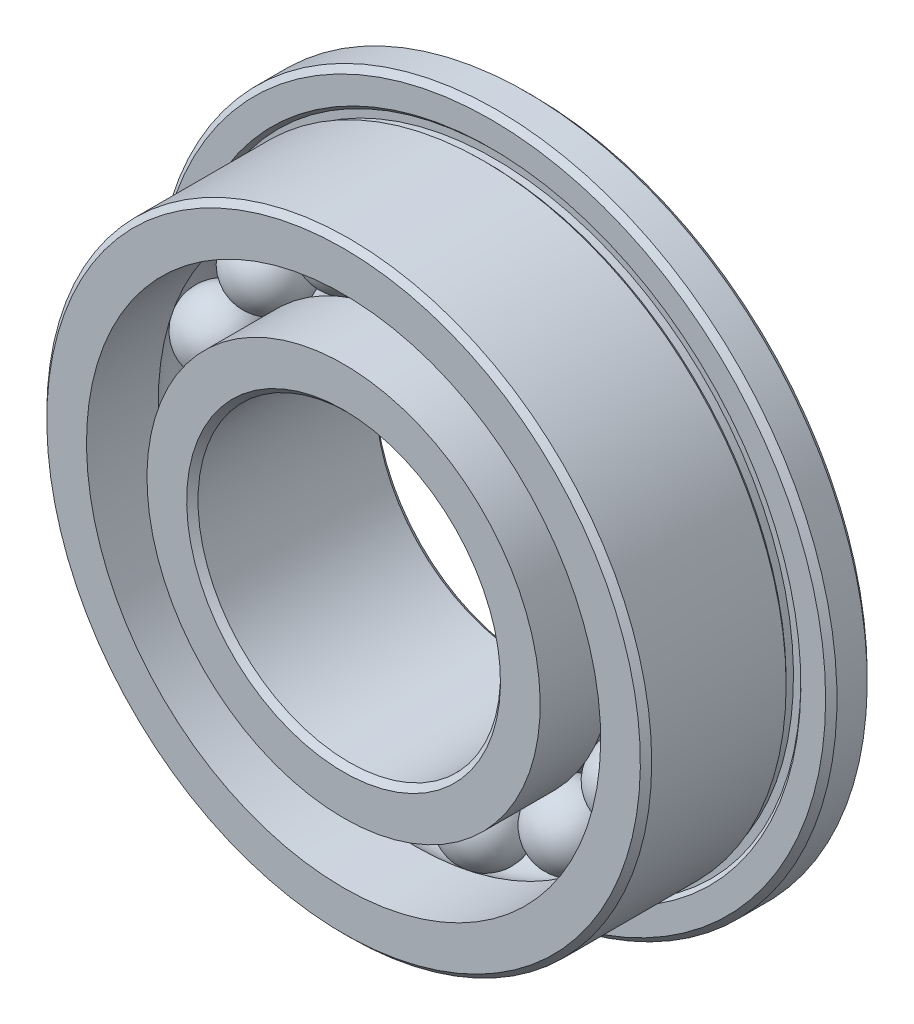
SolidWorks part; units mm, degrees
ref_plane "Front Plane" through (0, 0, 0) normal (0, 0, 1) x (1, 0, 0)
ref_plane "Top Plane" through (0, 0, 0) normal (0, 1, 0) x (1, 0, 0)
ref_plane "Right Plane" through (0, 0, 0) normal (1, 0, 0) x (0, 0, -1)
sketch "Sketch1" plane through (0, 0, 0) normal (1, 0, 0) x (0, 0, -1)
  line L0 (0, 8) -> (0, -8) construction
  line L1 (-2.5, 8) -> (2.5, 8) construction
  line L2 (0, 0) -> (2.5, 0) construction
  line L3 (2.5, 9) -> (2.5, -9) construction
  line L4 (2.5, -9) -> (1.4, -9) construction
  line L5 (2.5, 4) -> (0, 4) construction
  line L6 (2.5, 4) -> (2.5, -4) construction
  dimension "OD" = 16
  dimension "Width" = 5
  dimension "Flange Dia." = 18
  dimension "Flange Thickness" = 1.1
  dimension "ID" = 8
sketch "Sketch2" plane through (0, 0, 0) normal (1, 0, 0) x (0, 0, -1)
  line L0 (2.5, 9) -> (1.4, 9)
  line L1 (1.4, 9) -> (1.4, 8.1945)
  line L2 (1.2055, 8) -> (-2.5, 8)
  line L3 (-2.5, 8) -> (-2.5, 6.8)
  line L4 (-2.5, 6.8) -> (-0.6, 6.8)
  line L5 (2.5, 9) -> (2.5, -9) construction
  line L6 (2.5, 6.8) -> (2.5, 9)
  line L7 (2.5, 4) -> (-2.5, 4)
  line L8 (-2.5, 4) -> (-2.5, 5.2)
  line L9 (-2.5, 5.2) -> (-0.6, 5.2)
  line L10 (2.5, 5.2) -> (2.5, 4)
  line L11 (0, 8) -> (0, 4) construction
  line L12 (-1, 6) -> (1, 6) construction
  line L13 (0.6, 6.8) -> (2.5, 6.8)
  line L14 (0.6, 5.2) -> (2.5, 5.2)
  line L15 (1.4, 8.1945) -> (1.4972, 8.0972)
  line L16 (1.4972, 8.0972) -> (1.4972, 7.9028)
  line L17 (1.4972, 7.9028) -> (1.3028, 7.9028)
  line L18 (1.3028, 7.9028) -> (1.2055, 8)
  line L19 (1.4, 8) -> (1.4972, 7.9028) construction
  line L20 (1.4972, 8.0972) -> (1.3028, 7.9028) construction
  line L21 (1.2055, 8) -> (1.4, 8) construction
  line L22 (1.4, 8) -> (1.4, 8.1945) construction
  circle A0 centre (0, 6) radius 1 construction
  arc A1 (-0.6, 6.8) -> (0.6, 6.8) centre (0, 6) cw
  arc A2 (-0.6, 5.2) -> (0.6, 5.2) centre (0, 6) ccw
  dimension "D1" = 4
  dimension "Ball Dia." = 2
  dimension "D2" = 135
  dimension "D3" = 0.275
  dimension "D4" = 1.6
  dimension "Race Thikness" = 1.2
revolve "Revolve1" add sketch "Sketch2" angle 360 about L2
fillet "Fillet1" radius 0.15 3 edges at (0, -9, -2.5) (0, -9, -1.4) (0, -8, 2.5) profile chamfer
sketch "Sketch3" plane through (0, 0, 0) normal (0, 0, 1) x (1, 0, 0)
  line L0 (-4, 0) -> (4, 0) construction
  line L1 (-8, 0) -> (8, 0) construction
  point P5 (0, 0)
  dimension "ID2" = 8
  dimension "OD2" = 16
fillet "Fillet2" radius 0.15 2 edges at (0, -4, -2.5) (0, -4, 2.5) profile chamfer
sketch "Sketch7" plane through (0, 0, 0) normal (0, 0, 1) x (1, 0, 0)
  line L0 (0, 7) -> (0, 5)
  line L1 (0, 9) -> (0, -9) construction
  line L2 (-1.1832, 7) -> (0, 0) construction
  line L3 (0, 0) -> (1.1832, 7) construction
  line L4 (1.1832, 7) -> (-1.1832, 7) construction
  circle A0 centre (0, 6) radius 1 construction
  circle A1 centre (0, 0) radius 7 construction
  circle A2 centre (0, 0) radius 5 construction
  arc A4 (0, 7) -> (0, 5) centre (0, 6) ccw
  dimension "D1" = 19.188
revolve "Revolve3" add sketch "Sketch7" angle 360 about L0
pattern_circular "CirPattern3" count 15 over 360 about axis through (0, 0, 0) along (0, 0, -1) of bodies 107
sketch "Sketch8" [suppressed] plane through (0, 0, 0) normal (1, 0, 0) x (0, 0, -1)
  line L1 (-1, 2.9) -> (-0.76, 2.9)
  line L2 (-1, 2.9) -> (-1, 3.1)
  line L3 (-1, 3.1) -> (-0.76, 3.1)
  line L4 (-0.76, 2.9) -> (-0.76, 3.1)
  line L5 (1, 2.9) -> (0.76, 2.9)
  line L6 (1, 2.9) -> (1, 3.1)
  line L7 (1, 3.1) -> (0.76, 3.1)
  line L8 (0.76, 2.9) -> (0.76, 3.1)
  line L9 (1, 2.1) -> (0.76, 2.1)
  line L10 (1, 2.1) -> (1, 1.9)
  line L11 (1, 1.9) -> (0.76, 1.9)
  line L12 (0.76, 2.1) -> (0.76, 1.9)
  line L13 (-1, 2.1) -> (-0.76, 2.1)
  line L14 (-1, 2.1) -> (-1, 1.9)
  line L15 (-1, 1.9) -> (-0.76, 1.9)
  line L16 (-0.76, 2.1) -> (-0.76, 1.9)
  dimension "D1" = 0.4
  dimension "D2" = 0.48
revolve "Cut-Revolve1" [suppressed] cut sketch "Sketch8" angle 360 about L2
sketch "Sketch9" [suppressed] plane through (0, 0, 0) normal (1, 0, 0) x (0, 0, -1)
  line L0 (-0.76, 3.1) -> (-0.76, 2.7429)
  line L1 (-0.76, 2.7429) -> (-0.88, 2.535)
  line L2 (-0.88, 2.535) -> (-0.88, 1.96)
  line L3 (0.88, 1.96) -> (0.88, 1.9) construction
  line L4 (0.76, 3.1) -> (0.76, 2.7429)
  line L5 (0.76, 2.7429) -> (0.88, 2.535)
  line L6 (0.88, 2.535) -> (0.88, 1.96)
  line L7 (1, 1.9) -> (0.76, 1.9) construction
  line L8 (-0.82, 3.1) -> (-0.82, 2.7589)
  line L9 (-0.82, 2.7589) -> (-0.94, 2.5511)
  line L10 (-0.94, 2.5511) -> (-0.94, 1.96)
  line L11 (-0.76, 3.1) -> (-0.82, 3.1)
  line L12 (-0.88, 1.96) -> (-0.94, 1.96)
  line L13 (0.82, 3.1) -> (0.82, 2.7589)
  line L14 (0.82, 2.7589) -> (0.94, 2.5511)
  line L15 (0.94, 2.5511) -> (0.94, 1.96)
  line L16 (0.76, 3.1) -> (0.82, 3.1)
  line L17 (0.88, 1.96) -> (0.94, 1.96)
  line L18 (-0.76, 2.7429) -> (-0.76, 2.6) construction
  line L19 (0.76, 2.7429) -> (0.76, 3.1) construction
  line L20 (-0.76, 1.9) -> (-1, 1.9) construction
  line L22 (-0.88, 1.96) -> (-0.88, 1.9) construction
  dimension "D2" = 150
  dimension "D1" = 150
  dimension "D5" = 0.24
  dimension "D3" = 0.06
  dimension "D4" = 0.06
  dimension "D6" = 0.3571
revolve "Revolve4" [suppressed] add sketch "Sketch9" angle 360 about L2
ref_axis "Center Axis 1" through (0, 0, -0.66) along (0, 0, 1)
ref_plane "Contact Plane 1" through (0, 0, -1.4) normal (0, 0, 1) x (1, 0, 0)
equation "\"Ball Dia.@Sketch2\"=\"D1@Sketch2\"*.5"
equation "\"D3@Sketch2\"=\"Flange Thickness@Sketch1\"/4"
equation "\"D1@Fillet1\"=\"Race Thikness@Sketch2\"/8"
equation "\"ID2@Sketch3\" = \"ID@Sketch1\""
equation "\"OD2@Sketch3\" = \"OD@Sketch1\""
equation "\"D1@Fillet2\"=\"Race Thikness@Sketch2\"/8"
equation "\"D1@CirPattern3\"=360/\"D1@Sketch7\"-4"
equation "\"D1@Sketch8\"=\"Race Thikness@Sketch2\"/3"
equation "\"D2@Sketch8\"=\"Race Thikness@Sketch2\"/2.5"
equation "\"D3@Sketch9\"=\"D5@Sketch9\"/4"
equation "\"D4@Sketch9\"=\"D5@Sketch9\"/4"
equation "\"D1@Sketch9\"=\"D2@Sketch9\""
equation "\"D4@Sketch2\"=\"D1@Sketch2\"*.4"
